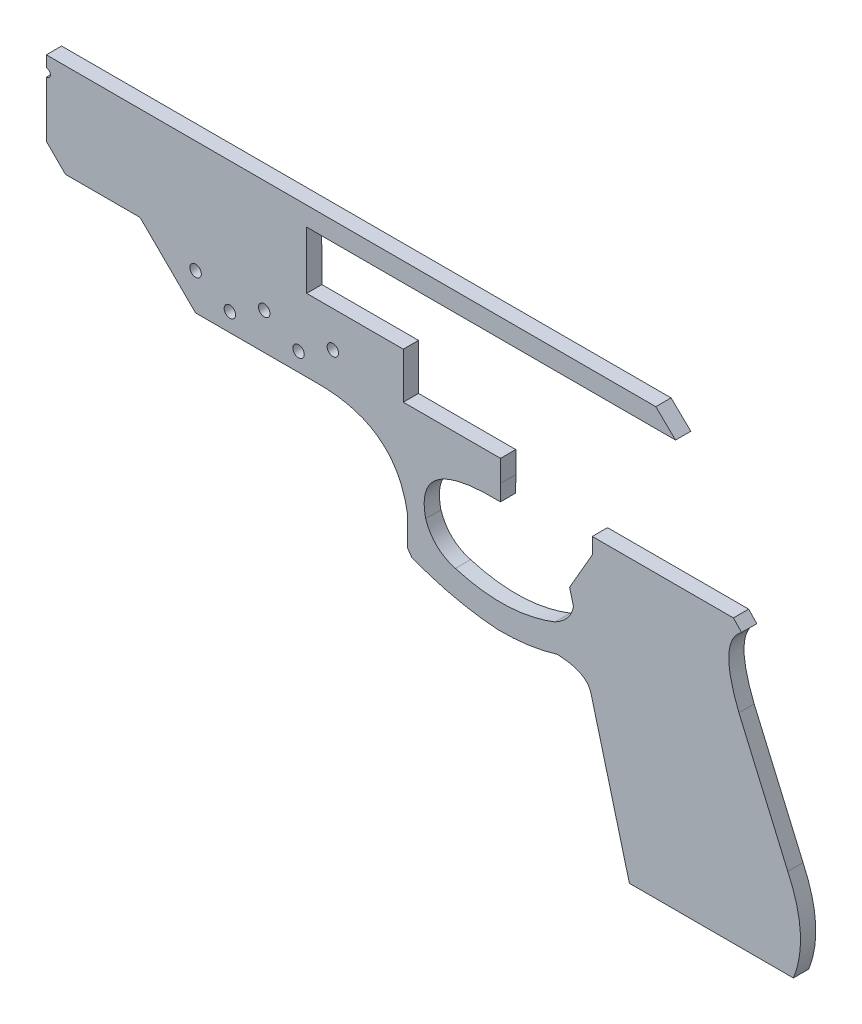
SolidWorks part; units mm, degrees
ref_plane "Front Plane" through (0, 0, 0) normal (0, 0, 1) x (1, 0, 0)
ref_plane "Top Plane" through (0, 0, 0) normal (0, 1, 0) x (1, 0, 0)
ref_plane "Right Plane" through (0, 0, 0) normal (1, 0, 0) x (0, 0, -1)
sketch "Sketch1" plane through (0, 0, 0) normal (0, 0, 1) x (1, 0, 0)
  line L0 (275.2156, 1168.292) -> (1376.0774, 1168.292) construction
  line L1 (2306.6441, 819.9826) -> (1936.601, 819.9826)
  line L2 (504.9927, 1197.919) -> (2103.2357, 1197.9722)
  line L3 (2103.2357, 1197.9722) -> (2154.992, 1147.9826)
  line L4 (750.7862, 951.5045) -> (554.9909, 951.506)
  line L5 (2306.6441, 819.9826) -> (2328.1936, 797.6651)
  line L6 (1441.0732, 997.4486) -> (1187.5655, 997.4486)
  line L7 (2286.5164, 840.8277) -> (2328.1936, 797.6651) construction
  line L8 (1186.9916, 1147.9826) -> (1187.5655, 997.4486)
  line L9 (1696.0732, 819.9826) -> (1696.0732, 877.0374)
  line L10 (1696.0732, 877.0374) -> (1441.0732, 877.0374) construction
  line L11 (2321.1197, 611.9262) -> (2449.3622, 315.5346)
  line L12 (2463.9434, 80.874) -> (2033.9434, 80.8955)
  line L13 (2033.9434, 80.8955) -> (1933.2319, 462.1503)
  line L14 (1695.7737, 777.9656) -> (1695.2927, 777.9826)
  line L15 (1441.0732, 877.0374) -> (1441.0732, 997.4486)
  line L16 (1696.0732, 877.0374) -> (1441.0732, 877.0374)
  line L17 (554.9909, 951.506) -> (504.9913, 1001.5063)
  line L19 (1936.601, 819.9826) -> (1936.601, 777.9826)
  line L20 (1936.601, 777.9826) -> (1877.0493, 674.8361)
  line L21 (2154.992, 1147.9826) -> (1186.9916, 1147.9826)
  line L23 (750.7862, 951.5045) -> (896.3629, 807.3806)
  line L24 (1214.0944, 807.3806) -> (896.3629, 807.3806)
  line L26 (1696.0732, 819.9826) -> (1695.7737, 777.9656)
  line L27 (504.9913, 1001.5063) -> (504.9925, 1147.2379)
  line L29 (1463.3169, 535.642) -> (1452.3791, 551.1255)
  line L30 (1452.3791, 551.1255) -> (1452.3791, 627.629)
  line L31 (1887.2046, 636.3922) -> (1877.0493, 674.8361)
  line L32 (504.9927, 1197.919) -> (504.9925, 1168.6)
  arc A0 (504.9925, 1168.6) -> (504.9925, 1147.2379) centre (504.9924, 1157.919) cw
  circle A1 centre (896.3629, 903.3806) radius 15
  circle A2 centre (986.3629, 855.3806) radius 15
  circle A3 centre (1076.3629, 903.3806) radius 15
  circle A4 centre (1166.3629, 855.3806) radius 15
  circle A5 centre (1256.3629, 903.3806) radius 15
  spline S0 degree 2 poles (1839.0283, 577.045) (1881.4356, 600.2191) (1887.2046, 636.3922) knots 0 0 0 0.760506 0.760506 0.760506
  spline S1 degree 2 poles (2449.3622, 315.5346) (2507.6289, 190.0982) (2463.9434, 80.874) knots 0 0 0 1 1 1
  spline S2 degree 2 poles (2321.1197, 611.9262) (2264.6079, 751.553) (2328.1936, 797.6651) knots 0 0 0 0.701234 0.701234 0.701234
  spline S3 degree 3 poles (1844.4882, 506.2174) (1896.9871, 504.8056) (1926.7795, 489.3172) (1933.8654, 459.7523) knots 0 0 0 0 0.746569 0.746569 0.746569 0.746569
  spline S4 degree 2 poles (1452.3791, 627.629) (1422.4271, 809.111) (1214.0944, 807.3806) knots 0 0 0 0.82397 0.82397 0.82397
  spline S5 degree 2 poles (1463.3169, 535.642) (1573.7016, 492.3812) (1689.3732, 484.6641) knots 0 0 0 1 1 1
  spline S6 degree 2 poles (1689.3732, 484.6641) (1769.5231, 483.4624) (1844.4882, 506.2174) knots 0 0 0 1 1 1
  spline S8 degree 2 poles (1695.2927, 777.9826) (1468.3908, 784.5404) (1499.6836, 641.8152) knots 0 0 0 1 1 1
  spline S9 degree 2 poles (1499.6836, 641.8152) (1519.6534, 584.0683) (1577.5301, 567.9309) knots 0 0 0 1 1 1
  spline S10 degree 2 poles (1577.5301, 567.9309) (1712.5573, 527.6653) (1839.0283, 577.045) knots 0 0 0 1 1 1
  dimension "D8" = 30
  dimension "D9" = 30
  dimension "D10" = 30
  dimension "D12" = 30
  dimension "D16" = 30
  dimension "D1" = 430
  dimension "D2" = 75.2
  dimension "D3" = 113.4
  dimension "D4" = 48
  dimension "D5" = 96
  dimension "D11" = 328
  dimension "D13" = 120
  dimension "D14" = 42
  dimension "D15" = 90
  dimension "D17" = 96
  dimension "D18" = 48
  dimension "D19" = 96
  dimension "D20" = 90
  dimension "D21" = 90
  dimension "D22" = 90
  dimension "D23" = 90
extrude "Boss-Extrude2" add sketch "Sketch1" along normal blind 40 contours S10 S9 S8 L14 L26 L9 L16 L15 L6 L21 L3 L2 L32 A0 L27 L17 L4 L23 L24 S4 L30 L29 S5 S6 S3 L13 L12 S1 L11 S2 L5 L1 L19 L20 L31 S0 A1 A2 A3 A4 region at (2301.0792, 793.0465, 0)
